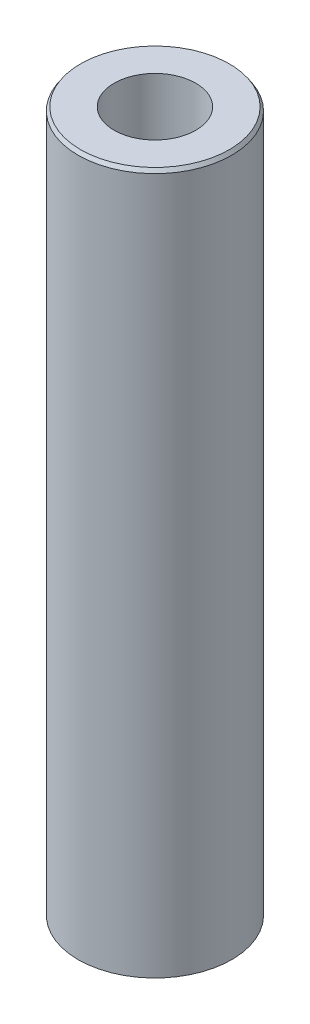
SolidWorks part; units mm, degrees
ref_plane "Front Plane" through (0, 0, 0) normal (0, 0, 1) x (1, 0, 0)
ref_plane "Top Plane" through (0, 0, 0) normal (0, 1, 0) x (1, 0, 0)
ref_plane "Right Plane" through (0, 0, 0) normal (1, 0, 0) x (0, 0, -1)
sketch "Sketch1" plane through (0, 0, 0) normal (0, 1, 0) x (1, 0, 0)
  circle A0 centre (0, 0) radius 55
  dimension "SHAFT_OD" = 110
extrude "Boss-Extrude1" add sketch "Sketch1" along normal blind 503.1858
sketch "Sketch2" plane through (0, 0, 0) normal (0, 1, 0) x (1, 0, 0)
  circle A0 centre (0, 0) radius 29.2359
  dimension "BORE_D" = 58.4719
extrude "Cut-Extrude1" cut sketch "Sketch2" along normal through all
chamfer "Chamfer1" distance 2.6143 angle 33.563 2 edges at (0, 503.1858, 55) (0, 0, 55) first distance on face at (0, 503.1858, 55) first distance on face at (0, 0, 29.2359)
